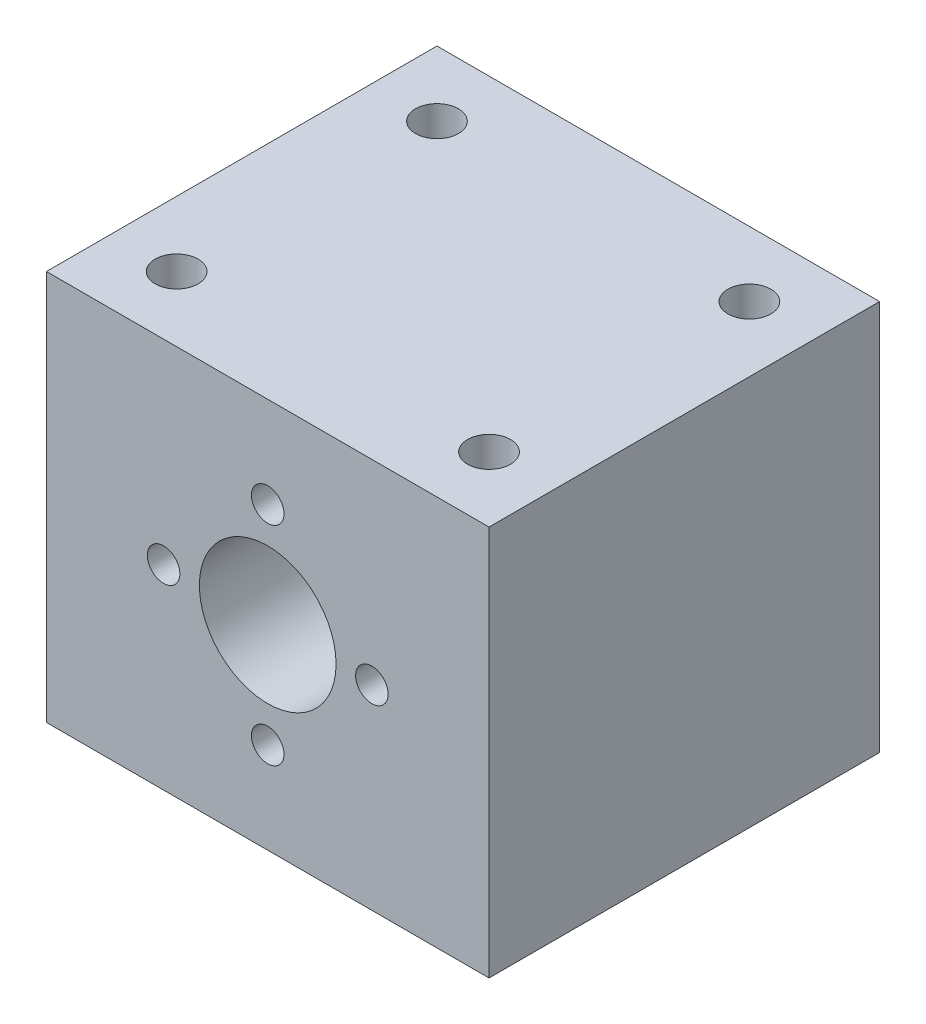
SolidWorks part; units mm, degrees
material "6061 合金"
ref_plane "前基準面" through (0, 0, 0) normal (0, 0, 1) x (1, 0, 0)
ref_plane "上基準面" through (0, 0, 0) normal (0, 1, 0) x (1, 0, 0)
ref_plane "右基準面" through (0, 0, 0) normal (1, 0, 0) x (0, 0, -1)
sketch "草圖1" plane through (0, 0, 0) normal (0, 0, 1) x (1, 0, 0)
  line L1 (-17, 15) -> (17, 15)
  line L2 (-17, 15) -> (-17, -15)
  line L3 (-17, -15) -> (17, -15)
  line L4 (17, 15) -> (17, -15)
  line L5 (-17, 15) -> (17, -15) construction
  line L6 (-17, -15) -> (17, 15) construction
  point P0 (0, 0)
  dimension "D1" = 34
  dimension "D2" = 30
extrude "填料-伸長1" add sketch "草圖1" along normal mid plane 30
sketch "草圖3" plane through (0, 0, 15) normal (0, 0, 1) x (1, 0, 0)
  circle A0 centre (0, 0) radius 5.25
  dimension "D1" = 10.5
extrude "除料-伸長1" cut sketch "草圖3" against normal through all
hole_wizard "M3x0.5 螺紋孔1" positions "草圖5" profile "草圖6" tap size "M3x0.5" standard "Ansi Metric"
sketch "草圖5" plane through (0, 0, 15) normal (0, 0, 1) x (1, 0, 0)
  line L3 (-8, 0) -> (8, 0) construction
  line L4 (0, -8) -> (0, 8) construction
  point P2 (8, 0)
  point P6 (-8, 0)
  point P34 (0, 8)
  point P37 (0, -8)
  dimension "D1" = 16
sketch "草圖6" plane through (8, 0, 15) normal (1, 0, 0) x (0, -1, 0)
  line L0 (0, 0) -> (0, 10.7511)
  line L1 (0, 10.7511) -> (1.25, 10)
  line L2 (1.25, 10) -> (1.25, 0)
  line L5 (1.25, 0) -> (0, 0)
  line L10 (0, 10.7511) -> (-1.25, 10) construction
  line L11 (0, -6.35) -> (0, 107.95) construction
  dimension "螺孔鑽直徑" = 2.5
  dimension "螺孔鑽深度" = 10
  dimension "導頭角度" = 118
hole_wizard "M4x0.7 螺紋孔1" positions "草圖7" profile "草圖8" tap size "M4x0.7" standard "Ansi Metric"
sketch "草圖7" plane through (0, 15, 0) normal (0, 1, 0) x (1, 0, 0)
  line L6 (-12, 10) -> (12, 10)
  line L7 (-12, 10) -> (-12, -10)
  line L8 (-12, -10) -> (12, -10)
  line L9 (12, 10) -> (12, -10)
  line L10 (-12, 10) -> (12, -10) construction
  line L11 (-12, -10) -> (12, 10) construction
  point P101 (12, -10)
  point P186 (-12, 10)
  point P187 (-12, -10)
  point P188 (12, 10)
  point P202 (0, 0)
  dimension "D1" = 24
  dimension "D2" = 20
sketch "草圖8" plane through (12, 15, 10) normal (1, 0, 0) x (0, 0, 1)
  line L0 (0, 0) -> (0, 20.9914)
  line L1 (0, 20.9914) -> (1.65, 20)
  line L2 (1.65, 20) -> (1.65, 0)
  line L5 (1.65, 0) -> (0, 0)
  line L10 (0, 20.9914) -> (-1.65, 20) construction
  line L11 (0, -6.35) -> (0, 107.95) construction
  dimension "螺孔鑽直徑" = 3.3
  dimension "螺孔鑽深度" = 20
  dimension "導頭角度" = 118
